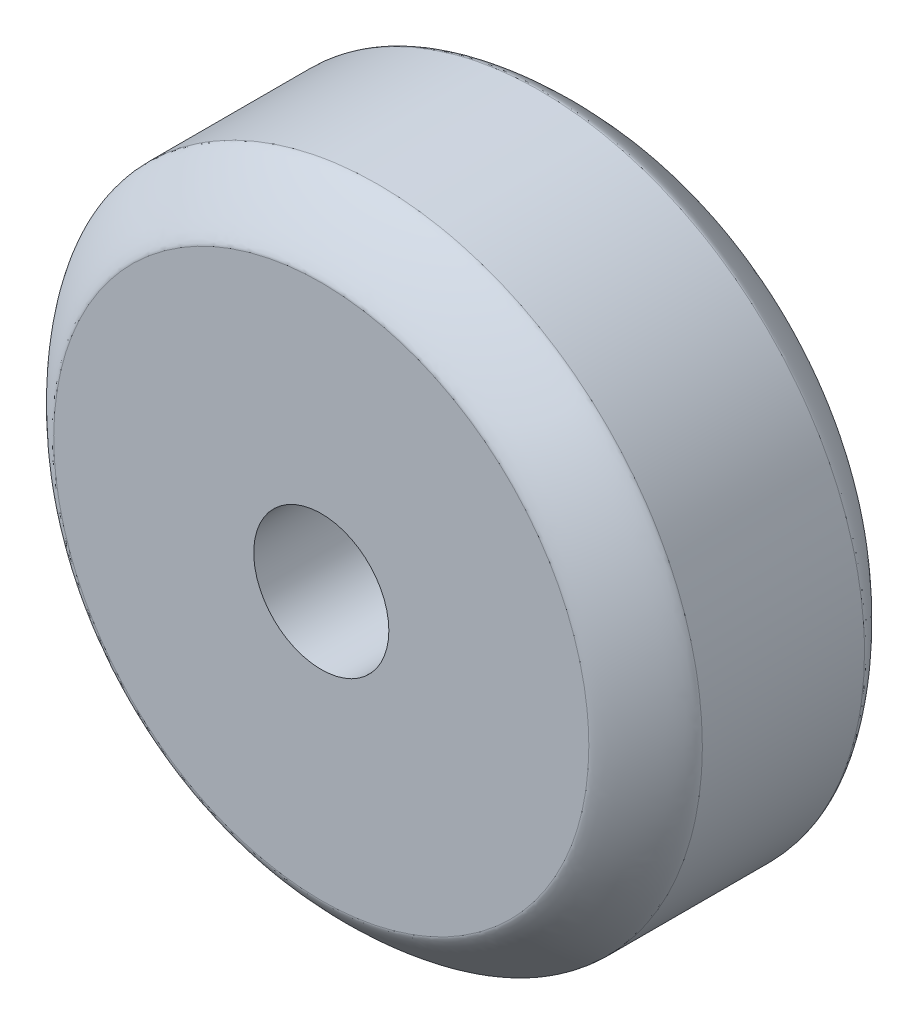
SolidWorks part; units mm, degrees
ref_plane "Front Plane" through (0, 0, 0) normal (0, 0, 1) x (1, 0, 0)
ref_plane "Top Plane" through (0, 0, 0) normal (0, 1, 0) x (1, 0, 0)
ref_plane "Right Plane" through (0, 0, 0) normal (1, 0, 0) x (0, 0, -1)
sketch "Sketch1" plane through (0, 0, 0) normal (0, 0, 1) x (1, 0, 0)
  circle A0 centre (0, 0) radius 12
  circle A1 centre (0, 0) radius 2.5
  dimension "D1" = 5
  dimension "D2" = 24
extrude "Boss-Extrude1" add sketch "Sketch1" along normal blind 10.2
fillet "Fillet1" radius 2.1 2 edges at (12, 0, 0) (12, 0, 10.2) conic radius 10
